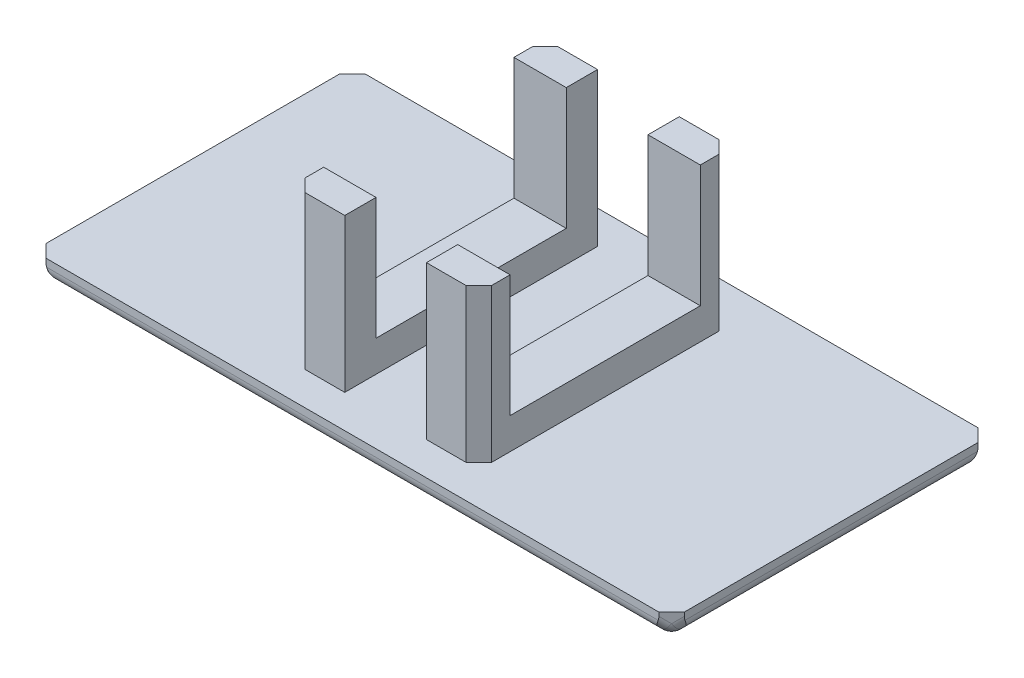
SolidWorks part; units mm, degrees
ref_plane "Front Plane" through (0, 0, 0) normal (0, 0, 1) x (1, 0, 0)
ref_plane "Top Plane" through (0, 0, 0) normal (0, 1, 0) x (1, 0, 0)
ref_plane "Right Plane" through (0, 0, 0) normal (1, 0, 0) x (0, 0, -1)
sketch "Sketch1" plane through (0, 0, 0) normal (0, 1, 0) x (1, 0, 0)
  line L1 (-25, 12.5) -> (25, 12.5)
  line L2 (-25, 12.5) -> (-25, -12.5)
  line L3 (-25, -12.5) -> (25, -12.5)
  line L4 (25, 12.5) -> (25, -12.5)
  line L5 (-25, 12.5) -> (25, -12.5) construction
  line L6 (-25, -12.5) -> (25, 12.5) construction
  point P0 (0, 0)
  dimension "D1" = 50
  dimension "D2" = 25
extrude "Boss-Extrude1" add sketch "Sketch1" along normal blind 3
sketch "Sketch2" plane through (0, 3, 0) normal (0, 1, 0) x (1, 0, 0)
  line L0 (0, 0) -> (-5.25, 0) construction
  line L1 (-1.65, 0) -> (1.65, 0) construction
  line L2 (0, -1.65) -> (0, 1.65) construction
  line L3 (-7.3, 9.9) -> (-3.2, 9.9)
  line L4 (-7.3, 9.9) -> (-7.3, -9.9)
  line L5 (-7.3, -9.9) -> (-3.2, -9.9)
  line L6 (-3.2, 9.9) -> (-3.2, -9.9)
  line L7 (-7.3, 9.9) -> (-3.2, -9.9) construction
  line L8 (-7.3, -9.9) -> (-3.2, 9.9) construction
  line L9 (7.3, -9.9) -> (3.2, -9.9)
  line L10 (3.2, 9.9) -> (3.2, -9.9)
  line L11 (7.3, 9.9) -> (3.2, 9.9)
  line L12 (7.3, 9.9) -> (7.3, -9.9)
  dimension "D1" = 5.25
  dimension "D2" = 4.1
  dimension "D3" = 19.8
extrude "Boss-Extrude2" add sketch "Sketch2" along normal blind 12
chamfer "Chamfer3" distance 1 angle 45 4 edges at (25, 1.5, 12.5) (25, 1.5, -12.5) (-25, 1.5, 12.5) (-25, 1.5, -12.5)
chamfer "Chamfer1" distance 2 angle 45 4 edges at (0, 0, -12.5) (-25, 0, 0) (0, 0, 12.5) (25, 0, 0)
fillet "Fillet1" radius 1 20 edges at (0, 0, 10.5) (23, 0, 0) (0, 0, -10.5) (-23, 0, 0) (-25, 2, 0) (0, 2, -12.5) (25, 2, 0) (0, 2, 12.5) (-24.75, 1.75, 11.75) (-24.75, 1.75, -11.75) (-24.25, 1.75, 12.25) (24.25, 1.75, 12.25) (-23.75, 0.75, 11.25) (24.75, 1.75, 11.75) (24.75, 1.75, -11.75) (23.75, 0.75, 11.25) (24.25, 1.75, -12.25) (-24.25, 1.75, -12.25) (-23.75, 0.75, -11.25) (23.75, 0.75, -11.25)
sketch "Sketch3" plane through (-7.3, 0, 0) normal (-1, 0, 0) x (0, 0, 1)
  line L0 (-9.9, 15) -> (9.9, 15) construction
  line L1 (-7.45, 15) -> (7.45, 15)
  line L2 (-7.45, 15) -> (-7.45, 5.45)
  line L3 (-7.45, 5.45) -> (7.45, 5.45)
  line L4 (0, 15) -> (0, 5.45)
  line L5 (-7.45, 15) -> (0, 5.45) construction
  line L6 (-7.45, 5.45) -> (0, 15) construction
  line L7 (0, -8.25) -> (0, 8.25) construction
  line L8 (-9.9, 15) -> (-9.9, 3) construction
  line L9 (-9.9, 3) -> (9.9, 3) construction
  line L10 (7.45, 15) -> (7.45, 5.45)
  point P4 (-3.725, 10.225)
  line M4 (9.9, 15) -> (-9.9, 15)
  dimension "D1" = 2.45
  dimension "D2" = 2.45
extrude "Cut-Extrude1" cut sketch "Sketch3" against normal through all contours L4 L1 L2 L3 | L10 L4 L3 M4 region at (-7.3, 10.225, -3.725) region at (-7.3, 10.225, 3.725)
chamfer "Chamfer2" distance 1 angle 45 4 edges at (7.3, 9, 9.9) (7.3, 9, -9.9) (-7.3, 9, -9.9) (-7.3, 9, 9.9)
